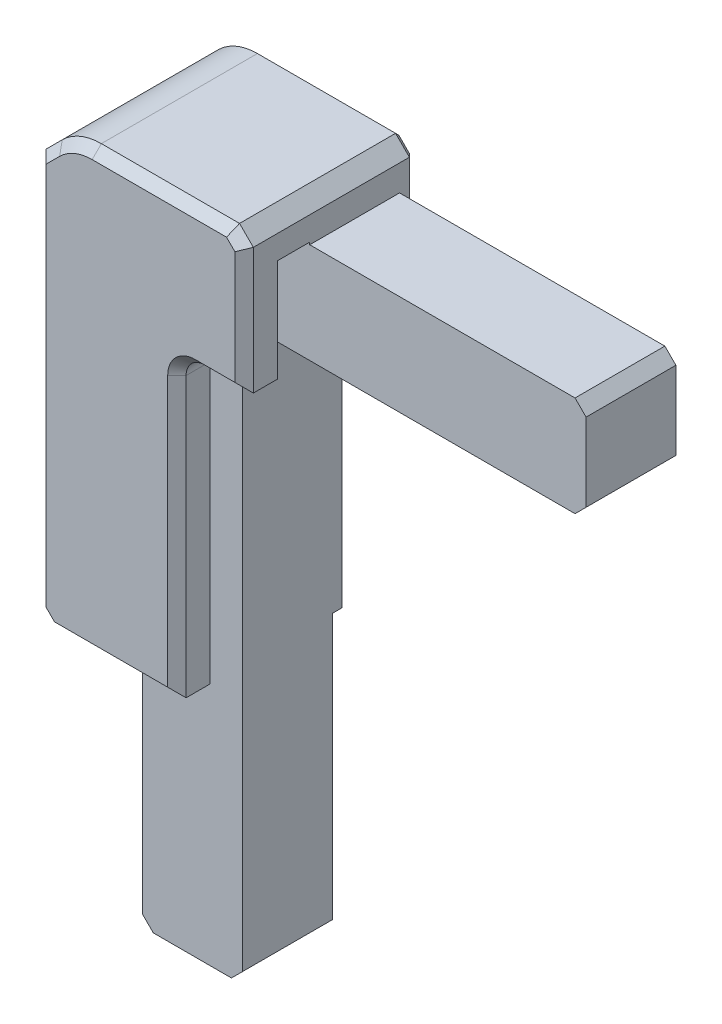
SolidWorks part; units mm, degrees
ref_plane "Front Plane" through (0, 0, 0) normal (0, 0, 1) x (1, 0, 0)
ref_plane "Top Plane" through (0, 0, 0) normal (0, 1, 0) x (1, 0, 0)
ref_plane "Right Plane" through (0, 0, 0) normal (1, 0, 0) x (0, 0, -1)
ref_plane "PZ 19.540" through (0, 0, 19.54) normal (0, 0, 1) x (1, 0, 0)
sketch "body sketch" plane through (0, 0, 19.54) normal (0, 0, 1) x (1, 0, 0)
  line L0 (-4.42, 7.07) -> (18.08, 7.07)
  line L1 (18.08, 7.07) -> (18.08, -8.13)
  line L2 (18.08, -8.13) -> (10.78, -8.13)
  line L3 (10.78, -8.13) -> (10.78, -40.43)
  line L4 (10.78, -40.43) -> (-4.42, -40.43)
  line L5 (-4.42, -40.43) -> (-4.42, 7.07)
extrude "body" add sketch "body sketch" along normal mid plane 11.42
ref_plane "PZ 20.375" through (0, 0, 20.375) normal (0, 0, 1) x (1, 0, 0)
sketch "side tongue sketch" plane through (0, 0, 20.375) normal (0, 0, 1) x (1, 0, 0)
  line L0 (10.78, -70.43) -> (-0.1, -70.43)
  line L1 (-0.1, -70.43) -> (-0.1, -39.43)
  line L2 (-0.1, -39.43) -> (10.78, -39.43)
  line L3 (10.78, -39.43) -> (10.78, -70.43)
extrude "side tongue" add sketch "side tongue sketch" along normal mid plane 9.75
sketch "end tongue sketch" plane through (0, 0, 20.375) normal (0, 0, 1) x (1, 0, 0)
  line L0 (48.08, -8.13) -> (17.08, -8.13)
  line L1 (17.08, -8.13) -> (17.08, 2.75)
  line L2 (17.08, 2.75) -> (48.08, 2.75)
  line L3 (48.08, 2.75) -> (48.08, -8.13)
extrude "end tongue" add sketch "end tongue sketch" along normal mid plane 9.75
ref_plane "PZ 23.100" through (0, 0, 23.1) normal (0, 0, 1) x (1, 0, 0)
sketch "web sketch" plane through (0, 0, 23.1) normal (0, 0, 1) x (1, 0, 0)
  line L0 (-4.42, 7.07) -> (18.08, 7.07)
  line L1 (18.08, 7.07) -> (18.08, 3)
  line L2 (18.08, 3) -> (-0.35, 3)
  line L3 (-0.35, 3) -> (-0.35, -40.43)
  line L4 (-0.35, -40.43) -> (-4.42, -40.43)
  line L5 (-4.42, -40.43) -> (-4.42, 7.07)
extrude "web" add sketch "web sketch" along normal mid plane 18.54
ref_plane "PZ 30.560" through (0, 0, 30.56) normal (0, 0, 1) x (1, 0, 0)
sketch "lip sketch" plane through (0, 0, 30.56) normal (0, 0, 1) x (1, 0, 0)
  line L0 (-4.42, 7.07) -> (18.08, 7.07)
  line L1 (18.08, 7.07) -> (18.08, -8.13)
  line L2 (18.08, -8.13) -> (10.78, -8.13)
  line L3 (10.78, -8.13) -> (10.78, -40.43)
  line L4 (10.78, -40.43) -> (-4.42, -40.43)
  line L5 (-4.42, -40.43) -> (-4.42, 7.07)
extrude "lip" add sketch "lip sketch" along normal mid plane 3.62
sketch "insert hole 1 sketch" plane through (0, 0, 19.54) normal (0, 0, 1) x (1, 0, 0)
  line L0 (3.58, -28.7) -> (-5.42, -28.7)
  line L1 (-5.42, -28.7) -> (-5.42, -24.5304)
  line L2 (-5.42, -24.5304) -> (-4.02, -25.9304)
  line L3 (-4.02, -25.9304) -> (1.98, -26.35)
  line L4 (1.98, -26.35) -> (3.58, -26.35)
  line L5 (3.58, -26.35) -> (3.58, -28.7)
revolve "insert hole 1" cut sketch "insert hole 1 sketch" angle 360 about L0
sketch "insert hole 2 sketch" plane through (0, 0, 19.54) normal (0, 0, 1) x (1, 0, 0)
  line L0 (3.58, -12.7) -> (-5.42, -12.7)
  line L1 (-5.42, -12.7) -> (-5.42, -8.5304)
  line L2 (-5.42, -8.5304) -> (-4.02, -9.9304)
  line L3 (-4.02, -9.9304) -> (1.98, -10.35)
  line L4 (1.98, -10.35) -> (3.58, -10.35)
  line L5 (3.58, -10.35) -> (3.58, -12.7)
revolve "insert hole 2" cut sketch "insert hole 2 sketch" angle 360 about L0
chamfer "bumper corner, bed side" distance 3.516 angle 45 1 edges at (-4.42, 7.07, 23.1) tangent propagation no
fillet "bumper corner" radius 6 1 edges at (-0.904, 7.07, 23.1) tangent propagation no
ref_plane "PZ 27.000" through (0, 0, 27) normal (0, 0, 1) x (1, 0, 0)
sketch "sheet corner relief sketch" plane through (0, 0, 27) normal (0, 0, 1) x (1, 0, 0)
  circle A0 centre (-0.35, 3) radius 1
extrude "sheet corner relief" cut sketch "sheet corner relief sketch" against normal mid plane 3.5
fillet "reveal corner" radius 2 1 edges at (10.78, -8.13, 30.56) tangent propagation no
fillet "body inside corner" radius 2 1 edges at (10.78, -8.13, 19.54) tangent propagation no
chamfer "arm ends" distance 1.5 angle 45 2 edges at (18.08, 7.07, 23.1) (-4.42, -40.43, 23.1) tangent propagation no
chamfer "tongue lead-in" distance 1.2 angle 45 4 edges at (48.08, -8.13, 20.375) (48.08, 2.75, 20.375) (10.78, -70.43, 20.375) (-0.1, -70.43, 20.375) tangent propagation no
chamfer "front face chamfer" distance 1 angle 45 11 edges at (15.43, -8.13, 32.37) (11.3658, -8.7158, 32.37) (10.78, -25.28, 32.37) (3.93, -40.43, 32.37) (-3.67, -39.68, 32.37) (-4.42, -17.688, 32.37) (-3.5407, 4.4333, 32.37) (-0.7148, 6.6133, 32.37) (9.0806, 7.07, 32.37) (17.33, 6.32, 32.37) (18.08, -1.28, 32.37)
chamfer "back face chamfer" distance 0.6 angle 45 11 edges at (-0.7148, 6.6133, 13.83) (-3.5407, 4.4333, 13.83) (-4.42, -17.688, 13.83) (-3.67, -39.68, 13.83) (3.93, -40.43, 13.83) (10.78, -25.28, 13.83) (11.3658, -8.7158, 13.83) (15.43, -8.13, 13.83) (18.08, -1.28, 13.83) (17.33, 6.32, 13.83) (9.0806, 7.07, 13.83)
equation "\"diffL\"= 608.8mm"
equation "\"diffW\"= 329.4mm"
equation "\"diffT\"= 2.9mm"
equation "\"chanSlotW\"= 12.9mm"
equation "\"chanSlotDepth\"= 11.13mm"
equation "\"chanFloor\"= 1.57mm"
equation "\"chanLeg\"= 12.7mm"
equation "\"lightL\"= 605mm"
equation "\"lightW\"= 331mm"
equation "\"lightH\"= 92mm"
equation "\"lightSideFlat\"= 30mm"
equation "\"lightSlopeLen\"= 33.1mm"
equation "\"lightWingDepth\"= 47.9mm"
equation "\"lightWingFlat\"= 90.2mm"
equation "\"lightChanW\"= 99.6mm"
equation "\"lightChanStand\"= 44.1mm"
equation "\"insFlangeD\"= 12.3mm"
equation "\"insFromEnd\"= 20.7mm"
equation "\"insUpSlope\"= 20.8mm"
equation "\"gaugeH\"= 10mm"
equation "\"gaugeStepLen\"= 14mm"
equation "\"gaugeStepW0\"= 13.1mm"
equation "\"gaugeStepDW\"= 0.2mm"
equation "\"gaugeSteps\"= 5mm"
equation "\"gaugeHandleLen\"= 30mm"
equation "\"gaugeHandleW\"= 24mm"
equation "\"gaugeSlot0\"= 3mm"
equation "\"gaugeSlotD\"= 0.1mm"
equation "\"gaugeSlotDepth\"= 8mm"
equation "\"gap\"= 25.4mm"
equation "\"edgeL\"= 1mm"
equation "\"edgeW\"= 0.75mm"
equation "\"proud\"= 1.5mm"
equation "\"seatClr\"= 0.15mm"
equation "\"tongueClrZ\"= 0.1mm"
equation "\"tongueClrX\"= 0.25mm"
equation "\"tongueLen\"= 30mm"
equation "\"armSide\"= 45mm"
equation "\"armEnd\"= 20mm"
equation "\"cornerCham\"= 3mm"
equation "\"brkW\"= 26mm"
equation "\"brkT\"= 7mm"
equation "\"brkSeatClr\"= 0.2mm"
equation "\"brkScrewSpan\"= 16mm"
equation "\"pilotD\"= 2.7mm"
equation "\"pilotDepth\"= 10mm"
equation "\"screwClrD\"= 3.9mm"
equation "\"jogBelow\"= 4mm"
equation "\"padT\"= 7mm"
equation "\"padLen\"= 31mm"
equation "\"m6Clr\"= 7mm"
equation "\"m6Slot\"= 3mm"
equation "\"flangeRelD\"= 17mm"
equation "\"flangeRelDepth\"= 1.5mm"
equation "\"relLen\"= 7mm"
equation "\"relDepth\"= 4mm"
equation "\"relLand\"= 2mm"
equation "\"knockN\"= 100mm"
equation "\"petgcfE\"= 3000mm"
equation "\"mockExtent\"= 110mm"
equation "\"relZnear\"= 9.4mm"
equation "\"relZfar\"= 23.4mm"
equation "\"headD\"= 8mm"
equation "\"headH\"= 2.5mm"
equation "\"headFromEnd\"= 6.8mm"
equation "\"headBack\"= 16.4mm"
equation "\"sideClr\"= 0.4mm"
equation "\"cornerRelR\"= 1.5mm"
equation "\"cornerRelBack\"= 0.6mm"
equation "\"endHeadH\"= 2.8mm"
equation "\"footClr\"= 1.2mm"
equation "\"footEndClr\"= 3.5mm"
equation "\"footLift\"= 6mm"
equation "\"footBlockClr\"= 0.5mm"
equation "\"footBack\"= 50mm"
equation "\"footFwd\"= 10mm"
equation "\"footBraceEnd\"= 3mm"
equation "\"footLoadN\"= 25mm"
equation "\"spacerLen\"= 60mm"
equation "\"spacerShort\"= 0.5mm"
equation "\"spacerCham\"= 0.8mm"
equation "\"spacerPerSide\"= 3mm"
equation "\"spacerPerEnd\"= 1mm"
equation "\"toolR\"= 9mm"
equation "\"visR\"= 4mm"
equation "\"edgeR\"= 1mm"
equation "\"bendOutR\"= 5mm"
equation "\"insideR\"= 2.5mm"
equation "\"footCornerR\"= 10mm"
equation "\"footFrontR\"= 8mm"
equation "\"braceKinkR\"= 12mm"
equation "\"bedCham\"= 1mm"
equation "\"bedChamSmall\"= 0.6mm"
equation "\"soleTopR\"= 2mm"
equation "\"cornerR\"= 6mm"
equation "\"rimInR\"= 1mm"
equation "\"insFlangeH\"= 1mm"
equation "\"insHoleFinishD\"= 4.5mm"
equation "\"insLen\"= 6.4mm"
equation "\"footToeTip\"= 4mm"
equation "\"cgInset\"= 4mm"
equation "\"lampWeightN\"= 51mm"
equation "\"frameWeightN\"= 10mm"
equation "\"bumpIn\"= 8mm"
equation "\"bumpH\"= 3mm"
equation "\"legBelowFront\"= 2mm"
equation "\"lipClr\"= 0.1mm"
equation "\"revealR\"= 2mm"
equation "\"frontCham\"= 1mm"
equation "\"insHoleBotD\"= 4.7mm"
equation "\"insTaperDeg\"= 8mm"
equation "\"insMouthCham\"= 0.4mm"
equation "\"leanDeg\"= 5mm"
equation "\"footTailT\"= 6mm"
equation "\"v1LeanDeg\"= 4.5mm"
equation "\"toeNoseR\"= 5mm"
equation "\"petgE\"= 2000mm"
equation "\"cheekT\"= 8mm"
equation "\"handleUp\"= 50mm"
equation "\"handleZ\"= -10mm"
equation "\"gripD\"= 19.05mm"
equation "\"gripClr\"= 0.5mm"
equation "\"bossWall\"= 5mm"
equation "\"bossLen\"= 14mm"
equation "\"socketFloor\"= 4mm"
equation "\"barEndClr\"= 1mm"
equation "\"lipH\"= 4mm"
equation "\"lipDeep\"= 6mm"
equation "\"stripT\"= 1.3mm"
equation "\"stripW\"= 12mm"
equation "\"stripClr\"= 0.5mm"
equation "\"stripBack\"= 3mm"
equation "\"endRelClr\"= 1mm"
equation "\"cornerScrewX\"= 5.5mm"
equation "\"cornerScrewZ\"= 6mm"
equation "\"cornerScrewD\"= 8.5mm"
equation "\"footTabIn\"= 33mm"
equation "\"footTabZ1\"= 50mm"
equation "\"footTabZ2\"= 19mm"
equation "\"footTabR\"= 8mm"
equation "\"landAx0\"= -17mm"
equation "\"landAz0\"= -30mm"
equation "\"landAx1\"= -3mm"
equation "\"landAz1\"= -18mm"
equation "\"landBx0\"= -60mm"
equation "\"landBz0\"= -43mm"
equation "\"landBx1\"= -46mm"
equation "\"landBz1\"= -27mm"
equation "\"sdLidW\"= 84.15mm"
equation "\"sdChanW\"= 80.19mm"
equation "\"sdLidStep\"= 1.7mm"
equation "\"sdInsRecess\"= 0.81mm"
equation "\"sdInsSpan\"= 59.21mm"
equation "\"sdJunkIn\"= 10.36mm"
equation "\"sdJunkH\"= 4.32mm"
equation "\"sdJunkLen\"= 110mm"
equation "\"sdHandleY\"= 0mm"
equation "\"sdInsDown\"= 21.3mm"
equation "\"sdSkirtH\"= 10.5mm"
equation "\"sdWallDown\"= 37mm"
equation "\"sdLidClr\"= 0.8mm"
equation "\"sdWasherT\"= 1.6mm"
equation "\"sdWasherD\"= 12mm"
equation "\"sdLegT\"= 5mm"
equation "\"sdLegBelow\"= 11mm"
equation "\"sdLegHalf\"= 46mm"
equation "\"sdSkirtSlope\"= 50mm"
equation "\"sdLipH\"= 5mm"
equation "\"sdLeadCham\"= 1mm"
equation "\"sdJunkSide\"= 1.5mm"
equation "\"sdRecessH\"= 6mm"
equation "\"sdRoofT\"= 6mm"
equation "\"sdOpenL\"= 114.3mm"
equation "\"sdOpenH\"= 44.45mm"
equation "\"sdGripD\"= 25mm"
equation "\"sdBendR\"= 18mm"
equation "\"sdBaseR\"= 8mm"
equation "\"sdEndMargin\"= 2mm"
equation "\"sdSlotW\"= 8mm"
equation "\"sdSlotFloat\"= 1mm"
equation "\"sdEdgeR\"= 2mm"
equation "\"sheetReliefR\"= 1mm"
